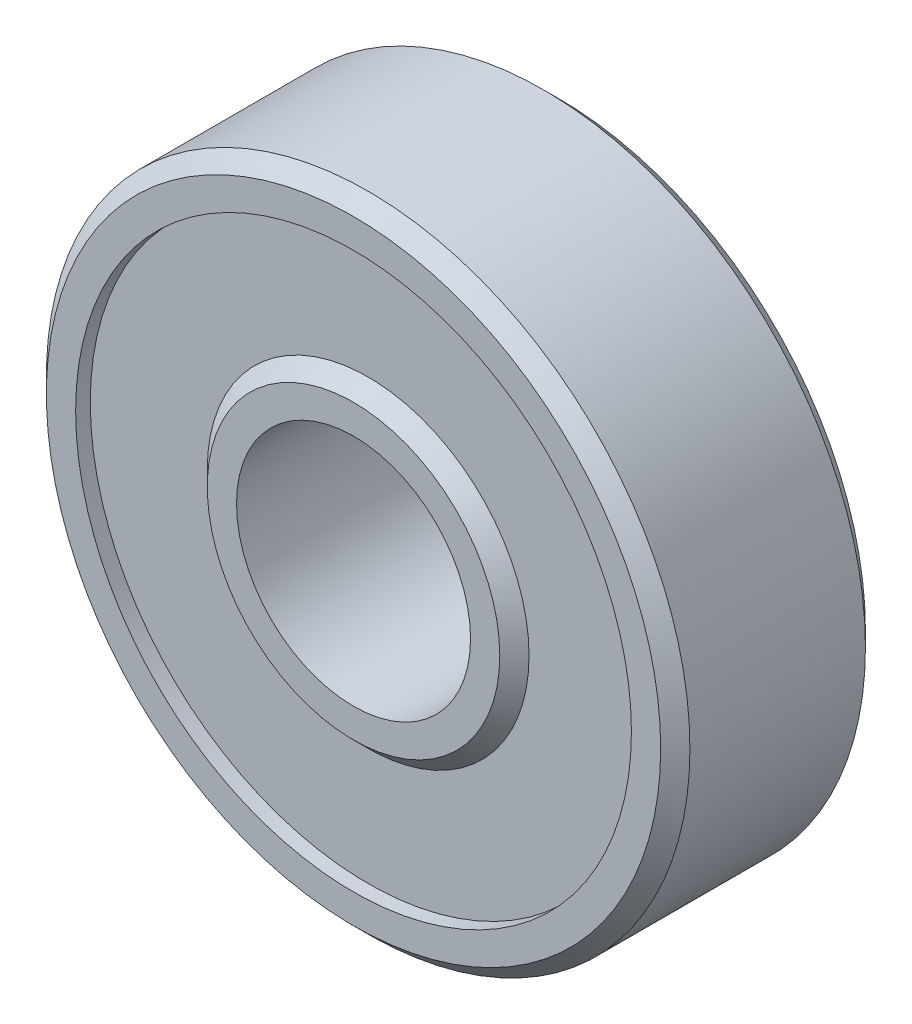
SolidWorks part; units mm, degrees
ref_plane "Front Plane" through (0, 0, 0) normal (0, 0, 1) x (1, 0, 0)
ref_plane "Top Plane" through (0, 0, 0) normal (0, 1, 0) x (1, 0, 0)
ref_plane "Right Plane" through (0, 0, 0) normal (1, 0, 0) x (0, 0, -1)
sketch "Sketch1" plane through (0, 0, 0) normal (0, 0, 1) x (1, 0, 0)
  circle A0 centre (0, 0) radius 11
  circle A1 centre (0, 0) radius 9.5
  circle A2 centre (0, 0) radius 5.5
  circle A3 centre (0, 0) radius 4
  dimension "D1" = 22
  dimension "D2" = 8
  dimension "D3" = 1.5
  dimension "D4" = 1.5
extrude "Boss-Extrude1" add sketch "Sketch1" along normal mid plane 7 contours A0 A1 | A2 A3 region at (-10.6889, 0, 0) region at (-5.3444, 0, 0)
extrude "Boss-Extrude2" add sketch "Sketch1<3>" along normal mid plane 6 contours A1 A2 region at (-9.2313, 0, 0)
sketch "Sketch1<3>" plane through (0, 0, 0) normal (0, 0, 1) x (1, 0, 0) same geometry as "Sketch1"
chamfer "Chamfer1" distance 0.5 angle 45 4 edges at (5.5, 0, 3.5) (5.5, 0, -3.5) (11, 0, -3.5) (11, 0, 3.5)
